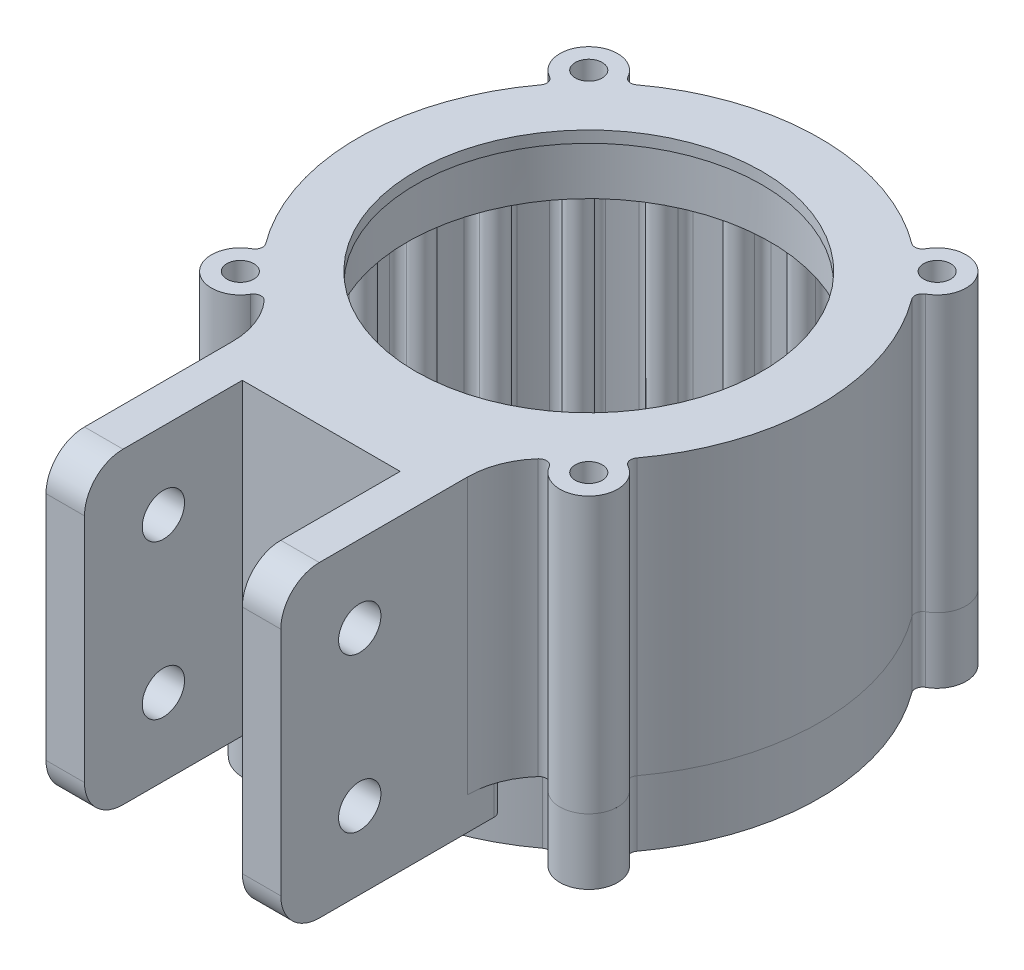
SolidWorks part; units mm, degrees
ref_plane "Front Plane" through (0, 0, 0) normal (0, 0, 1) x (1, 0, 0)
ref_plane "Top Plane" through (0, 0, 0) normal (0, 1, 0) x (1, 0, 0)
ref_plane "Right Plane" through (0, 0, 0) normal (1, 0, 0) x (0, 0, -1)
ref_axis "Housing Axis" through (0, 24.4803, 0) along (0, -1, 0)
sketch "Sketch1" plane through (0, 0, 0) normal (0, 1, 0) x (1, 0, 0)
  line L0 (0, 0) -> (27.1559, 4.0931) construction
  line L1 (0, 0) -> (27.1559, -4.0931) construction
  line L2 (0, 0) -> (26, 0) construction
  line L3 (27.1559, 4.0931) -> (29.6649, 4.4713)
  line L4 (27.1559, -4.0931) -> (29.6649, -4.4713)
  circle A0 centre (0, 0) radius 26 construction
  arc A1 (26.2079, 1.4855) -> (26.2079, -1.4855) centre (26, 0) ccw
  arc A2 (27.1559, 4.0931) -> (27.3422, 2.5694) centre (0, 0) cw
  arc A3 (27.3422, -2.5694) -> (27.1559, -4.0931) centre (0, 0) cw
  arc A4 (26.2079, 1.4855) -> (27.3422, 2.5694) centre (26.3466, 2.4759) ccw
  arc A5 (26.2079, -1.4855) -> (27.3422, -2.5694) centre (26.3466, -2.4759) cw
  arc A6 (26.2079, 1.4855) -> (26.2079, -1.4855) centre (0, 0) cw construction
  arc A7 (29.6649, 4.4713) -> (29.6649, -4.4713) centre (0, 0) cw
  point P14 (27.4605, -0.342)
  dimension "D1" = 52
  dimension "D2" = 3
  dimension "D5" = 1
  dimension "D6" = 30
  dimension "D3" = 17.143
  dimension "D4" = 0.25
extrude "Boss-Extrude1" add sketch "Sketch1" along normal mid plane 27.25
sketch "Sketch2" plane through (0, 13.625, 0) normal (0, 1, 0) x (1, 0, 0)
  circle A0 centre (0, 0) radius 30
  circle A1 centre (0, 0) radius 22.5
  circle A2 centre (0, 0) radius 30 construction
  dimension "D1" = 45
extrude "Boss-Extrude2" add sketch "Sketch2" along normal blind 8.5
pattern_circular "CirPattern1" count 21 over 360 about axis through (0, 24.4803, 0) along (0, -1, 0) of "Boss-Extrude1"
sketch "Sketch3" plane through (0, 22.125, 0) normal (0, -1, 0) x (-1, 0, 0)
  circle A0 centre (0, 0) radius 23.6
  dimension "D1" = 47.2
extrude "Cut-Extrude1" cut sketch "Sketch3" along normal through all from offset 1.5
sketch "Sketch4" plane through (0, 22.125, 0) normal (0, 1, 0) x (1, 0, 0)
  line L0 (-10.25, -55.25) -> (-10.25, -34.75)
  line L1 (-10.25, -34.75) -> (10.25, -34.75)
  line L2 (10.25, -34.75) -> (10.25, -55.25)
  line L3 (10.25, -55.25) -> (-10.25, -34.75) construction
  line L4 (0, -45) -> (0, 0) construction
  line L5 (10.25, -55.25) -> (15.25, -55.25)
  line L6 (15.25, -55.25) -> (15.25, -25.8348)
  line L7 (-10.25, -55.25) -> (-15.25, -55.25)
  line L8 (-15.25, -55.25) -> (-15.25, -25.8348)
  circle A0 centre (0, 0) radius 30 construction
  arc A1 (15.25, -25.8348) -> (-15.25, -25.8348) centre (0, 0) cw
  dimension "D3" = 5
  dimension "D1" = 20.5
  dimension "D2" = 45
extrude "Boss-Extrude3" add sketch "Sketch4" against normal blind 40
fillet "Fillet1" radius 10 2 edges at (15.25, 4.25, 25.8348) (-15.25, 4.25, 25.8348)
fillet "Fillet2" radius 1 2 edges at (-15.25, -15.75, 25.8348) (15.25, -15.75, 25.8348)
sketch "Sketch5" plane through (15.25, 0, 0) normal (1, 0, 0) x (0, 0, -1)
  line L0 (-45, 22.125) -> (-45, 12.125) construction
  line L1 (-55.25, 22.125) -> (-31.0232, 22.125) construction
  line L2 (-45, 12.125) -> (-45, -7.875) construction
  line L3 (-45, -7.875) -> (-45, -17.875) construction
  line L4 (-55.25, -17.875) -> (-27.5307, -17.875) construction
  line L5 (-55.25, 22.125) -> (-34.75, 22.125) construction
  circle A0 centre (-45, 12.125) radius 2.75
  circle A1 centre (-45, -7.875) radius 2.75
  dimension "D2" = 5.5
  dimension "D1" = 20
extrude "Cut-Extrude2" cut sketch "Sketch5" against normal through all both
fillet "Fillet3" radius 5 4 edges at (12.75, -17.875, 55.25) (-12.75, -17.875, 55.25) (12.75, 22.125, 55.25) (-12.75, 22.125, 55.25)
sketch "Sketch6" plane through (0, -13.625, 0) normal (0, -1, 0) x (1, 0, 0)
  line L0 (0, 0) -> (22.6274, 22.6274) construction
  line L1 (0, 0) -> (22.6274, -22.6274) construction
  line L2 (0, 0) -> (-22.6274, -22.6274) construction
  line L3 (0, 0) -> (-22.6274, 22.6274) construction
  line L4 (-22.6274, 22.6274) -> (22.6274, 22.6274) construction
  line L5 (22.6274, 22.6274) -> (22.6274, -22.6274) construction
  line L6 (-15.25, 31.0232) -> (15.25, 31.0232)
  circle A0 centre (22.6274, 22.6274) radius 1.75
  circle A1 centre (22.6274, -22.6274) radius 1.75
  circle A2 centre (-22.6274, -22.6274) radius 1.75
  circle A3 centre (-22.6274, 22.6274) radius 1.75
  arc A4 (24.4256, 19.3366) -> (19.3943, 24.5273) centre (22.6274, 22.6274) ccw
  arc A5 (19.3366, -24.4256) -> (24.4256, -19.3366) centre (22.6274, -22.6274) ccw
  arc A6 (-24.4256, -19.3366) -> (-19.3366, -24.4256) centre (-22.6274, -22.6274) ccw
  arc A7 (-19.3943, 24.5273) -> (-24.4256, 19.3366) centre (-22.6274, 22.6274) ccw
  arc A8 (-18.9375, 23.2674) -> (-15.25, 31.0232) centre (-25.25, 31.0232) ccw construction
  arc A9 (24.1017, 17.8636) -> (24.4256, 19.3366) centre (24.9051, 18.4591) cw
  arc A10 (15.25, 31.0232) -> (18.9375, 23.2674) centre (25.25, 31.0232) ccw construction
  arc A11 (-18.9375, 23.2674) -> (-18.9331, 23.271) centre (-25.25, 31.0232) ccw
  arc A12 (-17.8636, -24.1017) -> (17.8636, -24.1017) centre (0, 0) ccw
  arc A13 (15.25, 31.0232) -> (17.7857, 24.3685) centre (25.25, 31.0232) ccw
  arc A14 (-24.1017, 17.8636) -> (-24.1017, -17.8636) centre (0, 0) ccw
  arc A15 (24.1017, -17.8636) -> (24.1017, 17.8636) centre (0, 0) ccw
  arc A16 (-18.9375, 23.2674) -> (18.9375, 23.2674) centre (0, 0) ccw construction
  arc A17 (24.4256, -19.3366) -> (24.1017, -17.8636) centre (24.9051, -18.4591) cw
  arc A18 (17.8636, -24.1017) -> (19.3366, -24.4256) centre (18.4591, -24.9051) cw
  arc A19 (-19.3366, -24.4256) -> (-17.8636, -24.1017) centre (-18.4591, -24.9051) cw
  arc A20 (-24.4256, -19.3366) -> (-24.1017, -17.8636) centre (-24.9051, -18.4591) ccw
  arc A21 (-24.4256, 19.3366) -> (-24.1017, 17.8636) centre (-24.9051, 18.4591) cw
  arc A22 (-19.3943, 24.5273) -> (-17.7857, 24.3685) centre (-18.5322, 25.034) ccw
  arc A23 (17.7857, 24.3685) -> (19.3943, 24.5273) centre (18.5322, 25.034) ccw
  arc A24 (-17.7857, 24.3685) -> (-15.25, 31.0232) centre (-25.25, 31.0232) ccw
  circle A25 centre (0, 0) radius 27.4626
  arc A26 (21.1438, 17.5253) -> (19.0564, 19.775) centre (0, 0) ccw construction
  point P13 (0, 0)
  point P36 (-18.9331, -23.271)
  dimension "D1" = 4
  dimension "D3" = 3.5
  dimension "D4" = 7.5
  dimension "D5" = 1
  dimension "D2" = 32
extrude "Boss-Extrude4" add sketch "Sketch6" against normal up to surface (35.75 mm away) contours A24 A22 A7 A21 A14 A20 A6 A19 A12 A18 A5 A17 A15 A9 A4 A23 A13 L6 A25 A3 A2 A1 A0 region at (0, -13.625, 30.1674) up to face at (0, 22.125, 32.4982)
sketch "Sketch7" plane through (0, -13.625, 0) normal (0, -1, 0) x (1, 0, 0)
  arc A0 (-19.163, 24.0628) -> (-24.4256, 19.3366) centre (-22.6274, 22.6274) ccw
  arc A1 (-24.4256, -19.3366) -> (-19.3366, -24.4256) centre (-22.6274, -22.6274) ccw
  arc A2 (24.4256, 19.3366) -> (19.163, 24.0628) centre (22.6274, 22.6274) ccw
  arc A3 (19.3366, -24.4256) -> (24.4256, -19.3366) centre (22.6274, -22.6274) ccw
  circle A4 centre (-22.6274, 22.6274) radius 1.75 construction
  circle A5 centre (-22.6274, -22.6274) radius 1.75 construction
  circle A6 centre (22.6274, -22.6274) radius 1.75 construction
  circle A7 centre (22.6274, 22.6274) radius 1.75 construction
  circle A8 centre (-22.6274, 22.6274) radius 1.75
  circle A9 centre (-22.6274, -22.6274) radius 1.75
  circle A10 centre (22.6274, -22.6274) radius 1.75
  circle A11 centre (22.6274, 22.6274) radius 1.75
  arc A12 (-19.3943, 24.5273) -> (-24.4256, 19.3366) centre (-22.6274, 22.6274) ccw construction
  arc A13 (-24.4256, -19.3366) -> (-24.1017, -17.8636) centre (-24.9051, -18.4591) ccw construction
  arc A14 (-24.1017, 17.8636) -> (-24.1017, -17.8636) centre (0, 0) ccw construction
  arc A15 (-24.1017, 17.8636) -> (-24.4256, 19.3366) centre (-24.9051, 18.4591) ccw construction
  arc A16 (-24.4256, -19.3366) -> (-24.1017, -17.8636) centre (-24.9051, -18.4591) ccw
  arc A17 (-24.1017, 17.8636) -> (-24.1017, -17.8636) centre (0, 0) ccw
  arc A18 (-24.1017, 17.8636) -> (-24.4256, 19.3366) centre (-24.9051, 18.4591) ccw
  arc A22 (24.1017, -17.8636) -> (24.4256, -19.3366) centre (24.9051, -18.4591) ccw
  arc A23 (24.1017, -17.8636) -> (24.1017, 17.8636) centre (0, 0) ccw
  arc A24 (24.4256, 19.3366) -> (24.1017, 17.8636) centre (24.9051, 18.4591) ccw
  arc A25 (-17.8636, -24.1017) -> (-19.3366, -24.4256) centre (-18.4591, -24.9051) ccw
  arc A26 (-17.8636, -24.1017) -> (17.8636, -24.1017) centre (0, 0) ccw
  arc A27 (19.3366, -24.4256) -> (17.8636, -24.1017) centre (18.4591, -24.9051) ccw
  circle A28 centre (0, 0) radius 23.6
  circle A29 centre (0, 0) radius 23.6 construction
  arc A30 (17.8636, 24.1017) -> (-17.8636, 24.1017) centre (0, 0) ccw [skipped]
  arc A31 (17.8636, 24.1017) -> (19.3366, 24.4256) centre (18.4591, 24.9051) ccw [skipped]
  arc A32 (-19.3366, 24.4256) -> (-17.8636, 24.1017) centre (-18.4591, 24.9051) ccw [skipped]
  arc A33 (17.6411, 23.644) -> (-17.6411, 23.644) centre (0, 0) ccw
  arc A34 (13.7903, 26.6426) -> (-13.7903, 26.6426) centre (0, 0) ccw construction
  arc A35 (17.6411, 23.644) -> (19.163, 24.0628) centre (18.2391, 24.4455) ccw
  arc A36 (-17.6411, 23.644) -> (-19.163, 24.0628) centre (-18.2391, 24.4455) cw
  point P55 (0, 0)
  dimension "D1" = 4
  dimension "D2" = 0.5
extrude "Boss-Extrude5" add sketch "Sketch7" along normal blind 8.5 separate body
sketch "Sketch8" plane through (0, -22.125, 0) normal (0, -1, 0) x (1, 0, 0)
  circle A0 centre (0, 0) radius 22.5
  circle A1 centre (0, 0) radius 22.5 construction
  circle A2 centre (0, 0) radius 23.6 construction
  circle A3 centre (0, 0) radius 23.6
extrude "Boss-Extrude6" add sketch "Sketch8" against normal blind 1.5
sketch "Sketch9" plane through (0, -22.125, 0) normal (0, -1, 0) x (1, 0, 0)
  line L0 (0, 0) -> (-19.8823, 19.8823) construction
  line L1 (-27.291, 12.4736) -> (-12.4736, 27.291) construction
  line L2 (0, 0) -> (0, 29.5) construction
  circle A0 centre (-27.291, 12.4736) radius 2.35
  circle A1 centre (-12.4736, 27.291) radius 2.35
  arc A2 (17.6411, 23.644) -> (-17.6411, 23.644) centre (0, 0) ccw construction
  circle A3 centre (-12.4736, 27.291) radius 5
  circle A4 centre (-27.291, 12.4736) radius 5
  dimension "D1" = 20.955
  dimension "D2" = 4.7
  dimension "D5" = 10
  dimension "D3" = 28.1178
  dimension "D4" = 45
extrude "Boss-Extrude7" add sketch "Sketch9" along normal blind 2.856 and the other way blind 2
sketch "Sketch10" plane through (0, -24.981, 0) normal (0, -1, 0) x (1, 0, 0)
  circle A0 centre (-27.291, 12.4736) radius 2.35 construction
  circle A1 centre (-12.4736, 27.291) radius 2.35 construction
  circle A2 centre (-27.291, 12.4736) radius 2.35
  circle A3 centre (-12.4736, 27.291) radius 2.35
extrude "Cut-Extrude3" cut sketch "Sketch10" against normal blind 4
sketch "Sketch11" plane through (0, -20.125, 0) normal (0, 1, 0) x (1, 0, 0)
  circle A0 centre (-27.291, -12.4736) radius 5 construction
  circle A1 centre (-12.4736, -27.291) radius 5 construction
  circle A2 centre (-27.291, -12.4736) radius 5
  circle A3 centre (-12.4736, -27.291) radius 5
extrude "Boss-Extrude8" add sketch "Sketch11" against normal up to surface (0.856 mm away) up to face at (-26.2194, -20.981, 11.9838)
chamfer "Chamfer1" distance 6 angle 45 2 edges at (-27.2851, -20.125, 12.4709) (-12.263, -20.125, 26.8304)
sketch "Sketch12" plane through (0, -17.875, 0) normal (0, -1, 0) x (1, 0, 0)
  circle A0 centre (-12.4736, 27.291) radius 5.5
  circle A1 centre (-12.4736, 27.291) radius 5 construction
  dimension "D1" = 0.5
extrude "Cut-Extrude4" cut sketch "Sketch12" against normal up to vertex (3.75 mm away) up to point (-16.5617, -14.125, 24.4123)
sketch "Sketch13" plane through (0, -22.125, 0) normal (0, -1, 0) x (1, 0, 0)
  line L0 (-24.8256, 16.8431) -> (-30.3322, 20.579)
  line L1 (-30.3322, 20.579) -> (-20.2983, 29.9184)
  line L2 (-20.2983, 29.9184) -> (-16.5624, 24.4119)
  line L3 (-16.5624, 24.4119) -> (0, 0) construction
  line L4 (0, 0) -> (-24.8256, 16.8431) construction
  arc A0 (-22.7879, 18.8809) -> (-18.8942, 22.273) centre (-22.6274, 22.6274) ccw
  arc A1 (-22.7879, 18.8809) -> (-23.618, 18.4984) centre (-22.8307, 17.8818) ccw
  arc A2 (-24.1017, 17.8636) -> (-24.8352, 16.8289) centre (0, 0) ccw construction
  arc A3 (-18.5267, 22.9567) -> (-18.8942, 22.273) centre (-17.8987, 22.1785) ccw
  arc A4 (-16.5617, 24.4123) -> (-17.6411, 23.644) centre (0, 0) ccw construction
  arc A5 (-19.163, 24.0628) -> (-17.6411, 23.644) centre (-18.2391, 24.4455) ccw construction
  arc A6 (-24.8256, 16.8431) -> (-23.618, 18.4984) centre (0, 0) cw
  arc A8 (-16.5624, 24.4119) -> (-18.5267, 22.9567) centre (0, 0) ccw
  arc A10 (-16.5617, 24.4123) -> (-7.6216, 28.4985) centre (-12.4736, 27.291) ccw construction
  circle A11 centre (-27.291, 12.4736) radius 5 construction
  arc A12 (-19.163, 24.0628) -> (-24.4256, 19.3366) centre (-22.6274, 22.6274) ccw construction
  arc A13 (17.6411, 23.644) -> (-7.6216, 28.4985) centre (0, 0) ccw construction
  arc A14 (-28.9773, 7.7665) -> (-24.1017, -17.8636) centre (0, 0) ccw construction
extrude "Cut-Extrude5" cut sketch "Sketch13" against normal blind 3
equation "\"RotorRadius\"= 26mm"
equation "\"Eccentricity\"= 1.00mm"
equation "\"RollerRadius\"= 1.5mm"
equation "\"GearRatio\"= 20"
equation "\"RollerCount\"=\"GearRatio\" + 1"
equation "\"RotorThickness\"= 6mm"
equation "\"OutputRollerRadius\"= 1.5mm"
equation "\"OutputRollerCount\"= 6"
equation "\"OutputRollerHoleCircleRadius\"=\"RotorRadius\"- 4 * \"OutputRollerRadius\""
equation "\"RotorGap\"= 0.5mm"
equation "\"D1@Sketch1\"=\"RotorRadius\"*2"
equation "\"D2@Sketch1\"=2*\"RollerRadius\""
equation "\"rotorCount\"= 2"
equation "\"D1@Boss-Extrude1\"=(\"rotorCount\" + 2) * \"RotorThickness\" + 0.5mm * (\"rotorCount\" + 4.5)"
equation "\"D1@CirPattern1\"=\"GearRatio\" + 1"
equation "\"D3@Sketch1\"=360deg/(\"GearRatio\" + 1)"
